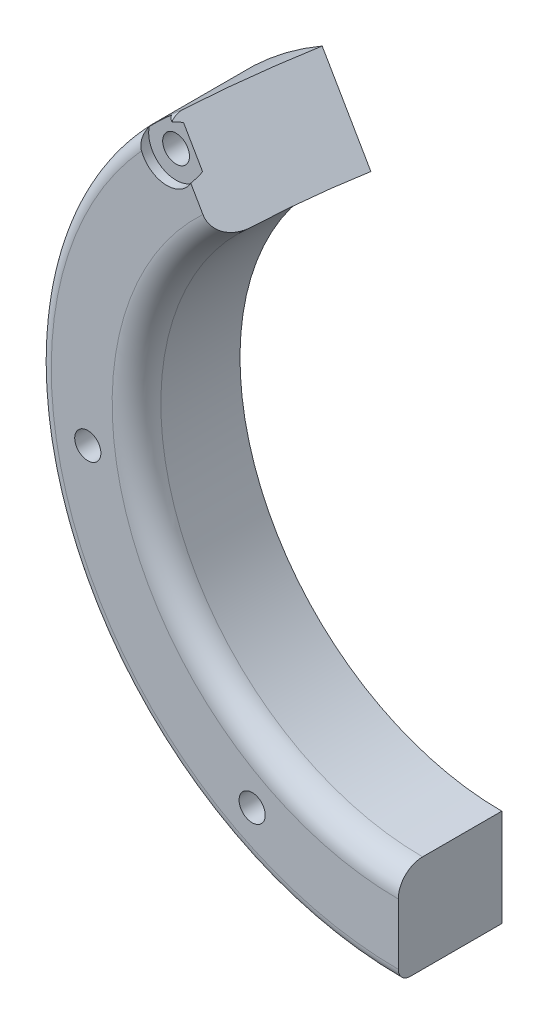
SolidWorks part; units mm, degrees
ref_plane "Front Plane" through (0, 0, 0) normal (0, 0, 1) x (1, 0, 0)
ref_plane "Top Plane" through (0, 0, 0) normal (0, 1, 0) x (1, 0, 0)
ref_plane "Right Plane" through (0, 0, 0) normal (1, 0, 0) x (0, 0, -1)
sketch "Sketch1" plane through (0, 0, 0) normal (0, 0, 1) x (1, 0, 0)
  line L0 (0, 59) -> (0, 43)
  line L1 (0, -43) -> (0, -59)
  arc A0 (0, 43) -> (0, -43) centre (0, 0) ccw
  arc A1 (0, 59) -> (0, -59) centre (0, 0) ccw
  dimension "D1" = 86
  dimension "D2" = 118
extrude "Boss-Extrude1" add sketch "Sketch1" along normal blind 17
sketch "Sketch2" plane through (0, 0, 17) normal (0, 0, 1) x (1, 0, 0)
  line L0 (0, 0) -> (0, 69.3776) construction
  circle A0 centre (-38, 40) radius 2.2
  dimension "D2" = 4.4
  dimension "D1" = 38
  dimension "D3" = 40
extrude "Cut-Extrude1" cut sketch "Sketch2" against normal through all
sketch "Sketch3" plane through (0, 0, 17) normal (0, 0, 1) x (1, 0, 0)
  line L0 (0, 0) -> (0, 64.381) construction
  line L1 (0, 0) -> (-48.7171, 84.3806)
  line L4 (0, 0) -> (0, 84.3806)
  line L5 (0, 84.3806) -> (-48.7171, 84.3806)
  dimension "D1" = 30
extrude "Cut-Extrude2" cut sketch "Sketch3" against normal through all
draft "Draft1" type of draft neutral plane draft angle 32 faces to draft 1 face at (-25.5, 44.1673, 8.5) neutral plane through (0, 0, 0) neutral plane normal (0, 0, -1) reverse direction yes parameters "D1"=32
sketch "Sketch4" plane through (0, 0, 17) normal (0, 0, 1) x (1, 0, 0)
  circle A0 centre (-38, 40) radius 4.5
  dimension "D1" = 9
extrude "Cut-Extrude3" cut sketch "Sketch4" against normal blind 1.5
fillet "Fillet1" radius 4 1 edges at (-39.8262, -16.2133, 17)
sketch "Sketch9" plane through (0, 0, 0) normal (0, 0, -1) x (-1, 0, 0)
  line L4 (40.9144, 37.1173) -> (41.9537, 41.0826)
  line L5 (41.9537, 41.0826) -> (39.0393, 43.9653)
  line L6 (39.0393, 43.9653) -> (35.0856, 42.8827)
  line L7 (35.0856, 42.8827) -> (21.021, 28.6634)
  line L8 (40.9144, 37.1173) -> (28.6052, 21.354)
  line L9 (21.021, 28.6634) -> (28.6052, 21.354)
  line L10 (35.2781, 37.6991) -> (36.7353, 36.2578) [skipped]
  line L11 (32.7795, 34.8899) -> (34.7563, 35.4311) [skipped]
  line L12 (35.0856, 42.8827) -> (34.566, 40.9) [skipped]
  arc A0 (35.4649, 37.5149) -> (35.4761, 42.4965) centre (38, 40) ccw construction
  dimension "D1" = 8.1984
  dimension "D2" = 20
extrude "Cut-Extrude4" cut sketch "Sketch9" against normal blind 4 from offset 2 offset against normal yes
sketch "Sketch10" plane through (0, 0, 0) normal (0, 0, -1) x (-1, 0, 0)
  line L0 (0, -59) -> (0, -43) construction
  circle A0 centre (24, -46) radius 1.25
  circle A1 centre (51, -8) radius 1.25
  dimension "D1" = 2.5
  dimension "D2" = 2.5
  dimension "D3" = 24
  dimension "D4" = 13
  dimension "D5" = 51
  dimension "D6" = 51
extrude "Cut-Extrude5" cut sketch "Sketch10" against normal through all
sketch "Sketch11" plane through (0, 0, 17) normal (0, 0, 1) x (1, 0, 0)
  circle A0 centre (-51, -8) radius 2.15
  circle A1 centre (-24, -46) radius 2.15
  dimension "D1" = 4.3
  dimension "D2" = 4.3
extrude "Cut-Extrude6" cut sketch "Sketch11" against normal blind 14
fillet "Fillet2" radius 2 2 edges at (-38.5234, 44.6872, 17) (-54.3283, -23.0094, 17)
